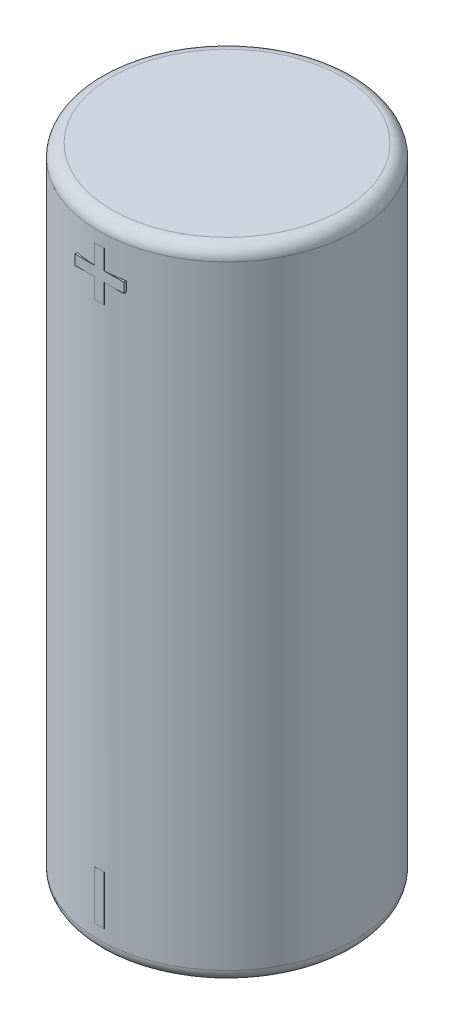
SolidWorks part; units mm, degrees
ref_plane "Front Plane" through (0, 0, 0) normal (0, 0, 1) x (1, 0, 0)
ref_plane "Top Plane" through (0, 0, 0) normal (0, 1, 0) x (1, 0, 0)
ref_plane "Right Plane" through (0, 0, 0) normal (1, 0, 0) x (0, 0, -1)
sketch "Sketch1" plane through (0, 0, 0) normal (0, 1, 0) x (1, 0, 0)
  circle A0 centre (0, 0) radius 13
  dimension "D1" = 26
extrude "Boss-Extrude1" add sketch "Sketch1" along normal blind 65
fillet "Fillet1" radius 1.27 1 edges at (0, 65, 13)
fillet "Fillet2" radius 1.27 1 edges at (0, 0, 13)
ref_plane "Plane1" through (0, 0, 13) normal (0, 0, 1) x (1, 0, 0)
sketch "Sketch2" plane through (0, 0, 13) normal (0, 0, 1) x (1, 0, 0)
  line L0 (11.73, 65) -> (-11.73, 65) construction
  line L1 (11.73, 65) -> (-11.73, 65)
  line L2 (0, 65) -> (0, 0) construction
  line L4 (-0.5, 62.5) -> (0.5, 62.5)
  line L5 (-0.5, 62.5) -> (-0.5, 57.5)
  line L6 (-0.5, 57.5) -> (0.5, 57.5)
  line L7 (0.5, 62.5) -> (0.5, 57.5)
  line L8 (-2.5, 60.5) -> (2.5, 60.5)
  line L9 (-2.5, 60.5) -> (-2.5, 59.5)
  line L10 (-2.5, 59.5) -> (2.5, 59.5)
  line L11 (2.5, 60.5) -> (2.5, 59.5)
  line L12 (-0.5, 7.5) -> (0.5, 7.5)
  line L13 (-0.5, 7.5) -> (-0.5, 2.5)
  line L14 (-0.5, 2.5) -> (0.5, 2.5)
  line L15 (0.5, 7.5) -> (0.5, 2.5)
  point P13 (0, 60)
  point P18 (0, 5)
  dimension "D1" = 5
  dimension "D2" = 5
  dimension "D3" = 1
  dimension "D4" = 1
  dimension "D5" = 0.5
  dimension "D6" = 2.5
  dimension "D7" = 5
  dimension "D8" = 0.5
  dimension "D9" = 2.5
  dimension "D10" = 1
  dimension "D11" = 5
  dimension "D12" = 5
  dimension "D13" = 2.5
  dimension "D14" = 0.5
extrude "Boss-Extrude2" add sketch "Sketch2" against normal blind 10 contours L2 L12 L13 L14 | L12 L2 L14 L15 | L5 L6 L7 L4 | L8 L11 L10 L9 region at (0.25, 5, 13) region at (-0.25, 5, 13)
sketch "Sketch3" plane through (0, 65, 0) normal (0, 1, 0) x (1, 0, 0)
  point P0 (0, 0)
  point P1 (0, 0)
sketch "Sketch4" plane through (0, 0, 0) normal (0, -1, 0) x (-1, 0, 0)
  point P0 (0, 0)
  point P1 (0, 0)
